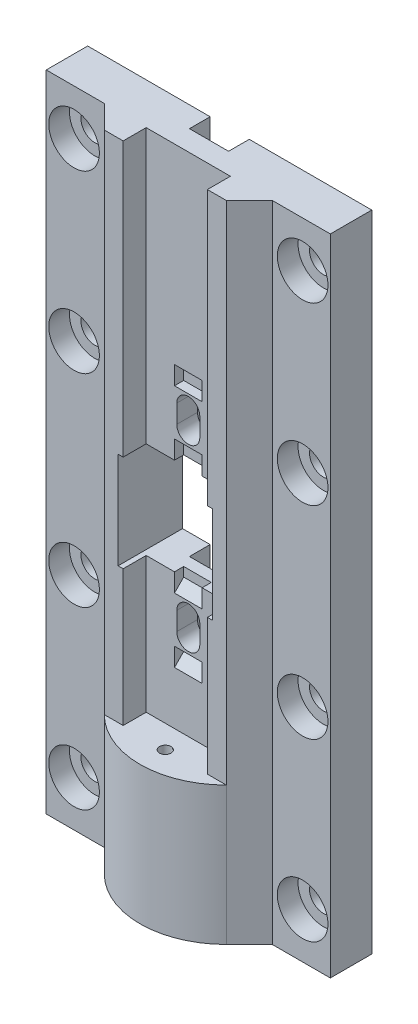
SolidWorks part; units mm, degrees
ref_plane "Top Plane" through (0, 0, 0) normal (0, 0, 1) x (1, 0, 0)
ref_plane "Right Plane" through (0, 0, 0) normal (0, 1, 0) x (1, 0, 0)
ref_plane "Front Plane" through (0, 0, 0) normal (1, 0, 0) x (0, 0, -1)
sketch "Sketch1" plane through (0, 0, 0) normal (0, 0, 1) x (1, 0, 0)
  line L0 (30.861, -28.956) -> (30.861, 28.956) construction
  line L1 (30.861, 28.956) -> (4.25, 28.956)
  line L2 (30.861, 28.956) -> (30.861, -41.044)
  line L3 (30.861, -41.044) -> (4.25, -41.044)
  line L4 (-30.861, 28.956) -> (-30.861, -41.044)
  line L5 (30.861, 28.956) -> (19.431, 28.956) construction
  line L6 (-30.861, -28.956) -> (-30.861, 28.956) construction
  line L8 (-24.8158, -19.05) -> (24.8412, -19.05) construction
  line L9 (-24.8158, -19.05) -> (-24.8158, 19.05) construction
  line L10 (-24.8158, 19.05) -> (24.8412, 19.05) construction
  line L11 (24.8412, -19.05) -> (24.8412, 19.05) construction
  line L12 (-4.25, 28.956) -> (-30.861, 28.956)
  line L14 (-4.25, -41.044) -> (-4.25, 28.956)
  line L16 (4.25, -41.044) -> (4.25, 28.956)
  line L17 (-4.25, -41.044) -> (-30.861, -41.044)
  circle A0 centre (24.8412, 19.05) radius 3
  circle A1 centre (24.8412, -19.05) radius 3
  circle A2 centre (-24.8158, -19.05) radius 3
  circle A3 centre (-24.8158, 19.05) radius 3
  arc A4 (-24.8158, 16.3957) -> (-24.8158, 21.7043) centre (-24.8158, 19.05) ccw construction
  arc A5 (24.8412, -21.7043) -> (24.8412, -16.3957) centre (24.8412, -19.05) ccw construction
  dimension "D1" = 6
  dimension "D2" = 70
  dimension "D3" = 8.5
extrude "Boss-Extrude1" add sketch "Sketch1" along normal blind 4.5
sketch "Sketch2" plane through (0, 0, 4.5) normal (0, 0, 1) x (1, 0, 0)
  line L1 (-30.861, 28.956) -> (30.861, 28.956)
  line L2 (-30.861, 28.956) -> (-30.861, -41.044)
  line L3 (-30.861, -41.044) -> (30.861, -41.044)
  line L4 (30.861, 28.956) -> (30.861, -41.044)
  circle A0 centre (24.8412, 19.05) radius 3 construction
  circle A1 centre (24.8412, -19.05) radius 3 construction
  circle A2 centre (-24.8158, 19.05) radius 3 construction
  circle A3 centre (-24.8158, -19.05) radius 3 construction
  circle A4 centre (24.8412, 19.05) radius 3 construction
  circle A5 centre (24.8412, -19.05) radius 3 construction
  circle A6 centre (-24.8158, 19.05) radius 3 construction
  circle A7 centre (-24.8158, -19.05) radius 3 construction
  circle A8 centre (24.8412, -19.05) radius 5.5
  circle A9 centre (-24.8158, -19.05) radius 5.5
  circle A10 centre (-24.8158, 19.05) radius 5.5
  circle A11 centre (24.8412, 19.05) radius 5.5
  dimension "D1" = 2.5
extrude "Boss-Extrude2" add sketch "Sketch2" along normal blind 4.5
sketch "Sketch3" plane through (0, 0, 9) normal (0, 0, 1) x (1, 0, 0)
  line L0 (-30.861, -41.044) -> (30.861, -41.044) construction
  line L1 (13.25, -41.044) -> (10.25, -41.044)
  line L2 (13.25, -41.044) -> (13.25, 28.956)
  line L3 (13.25, 28.956) -> (10.25, 28.956)
  line L4 (-13.25, -41.044) -> (-13.25, 28.956)
  line L5 (30.861, 28.956) -> (-30.861, 28.956) construction
  line L6 (-10.25, -41.044) -> (-13.25, -41.044)
  line L8 (10.25, -41.044) -> (10.25, 28.956)
  line L10 (-10.25, -41.044) -> (-10.25, 28.956)
  line L11 (-10.25, 28.956) -> (-13.25, 28.956)
  line L12 (30.861, -41.044) -> (13.25, -41.044) construction
  line L13 (-13.25, -41.044) -> (-30.861, -41.044) construction
  dimension "D1" = 20.5
  dimension "D2" = 3
extrude "Boss-Extrude3" add sketch "Sketch3" along normal blind 5
chamfer "Chamfer1" distance 5 angle 45 2 edges at (-13.25, -6.044, 9) (13.25, -6.044, 9)
sketch "Sketch4" plane through (0, 0, 9) normal (0, 0, 1) x (1, 0, 0)
  line L0 (-10.25, -41.044) -> (-10.25, 28.956) construction
  line L1 (10.25, -41.044) -> (-10.25, -41.044)
  line L2 (10.25, -41.044) -> (10.25, -30.544)
  line L3 (10.25, -30.544) -> (-10.25, -30.544)
  line L4 (-10.25, -41.044) -> (-10.25, -30.544)
  line L5 (0, -23.544) -> (0, -19.544) construction
  line L6 (-2.5, -23.544) -> (-2.5, -19.544)
  line L7 (2.5, -23.544) -> (2.5, -19.544)
  arc A0 (-2.5, -23.544) -> (2.5, -23.544) centre (0, -23.544) ccw
  arc A1 (2.5, -19.544) -> (-2.5, -19.544) centre (0, -19.544) ccw
  point P10 (0, -21.544)
  dimension "D2" = 2.5
  dimension "D1" = 10.5
  dimension "D3" = 7
  dimension "D4" = 4
extrude "Cut-Extrude1" cut sketch "Sketch4" against normal through all both and the other way through all
mirror "Mirror1" about plane through (30.861, -41.044, 4.5) normal (0, 1, 0) of bodies 106
ref_plane "Plane1" through (0, -41.044, 0) normal (0, -1, 0) x (-1, 0, 0)
sketch "Sketch5" plane through (0, -111.044, 0) normal (0, -1, 0) x (1, 0, 0)
  line L0 (-18.25, 9) -> (-13.25, 14) construction
  line L2 (-13.25, 14) -> (13.25, 14) construction
  line L3 (-13.25, 14) -> (-13.25, 9)
  line L4 (-13.25, 9) -> (13.25, 9)
  line L5 (13.25, 14) -> (13.25, 9)
  arc A0 (-13.25, 14) -> (13.25, 14) centre (0, 0.75) cw
  circle A1 centre (0, 14) radius 1.25
  dimension "D1" = 2.5
extrude "Boss-Extrude4" add sketch "Sketch5" against normal blind 30
sketch "Sketch6" plane through (0, 0, 9) normal (0, 0, 1) x (1, 0, 0)
  line L0 (10.25, 28.956) -> (-10.25, 28.956) construction
  line L1 (-10.25, -30.544) -> (-9.15, -30.544)
  line L2 (-10.25, -30.544) -> (-10.25, 28.956)
  line L3 (-10.25, 28.956) -> (-9.15, 28.956)
  line L4 (-9.15, -30.544) -> (-9.15, 28.956)
  line L6 (10.25, -30.544) -> (9.15, -30.544)
  line L7 (10.25, -30.544) -> (10.25, 28.956)
  line L8 (10.25, 28.956) -> (9.15, 28.956)
  line L9 (9.15, -30.544) -> (9.15, 28.956)
  dimension "D1" = 18.3
extrude "Boss-Extrude5" add sketch "Sketch6" along normal up to surface (5 mm away) up to face at (11.75, -26.044, 14)
sketch "Sketch7" plane through (0, 0, 9) normal (0, 0, 1) x (1, 0, 0)
  line L0 (0, -16.544) -> (0, -30.544) construction
  line L1 (3, -12.544) -> (-3, -12.544)
  line L2 (3, -12.544) -> (3, -16.544)
  line L3 (3, -16.544) -> (-3, -16.544)
  line L4 (-3, -12.544) -> (-3, -16.544)
  line L5 (9.15, -30.544) -> (-9.15, -30.544) construction
  line L7 (3, -30.544) -> (-3, -30.544)
  line L8 (3, -30.544) -> (3, -26.544)
  line L9 (3, -26.544) -> (-3, -26.544)
  line L10 (-3, -30.544) -> (-3, -26.544)
  dimension "D1" = 6
  dimension "D2" = 18
  dimension "D3" = 14
  dimension "D4" = 4
extrude "Cut-Extrude2" cut sketch "Sketch7" against normal blind 2
chamfer "Chamfer2" distance 2 angle 45 1 edges at (0, -26.544, 7)
chamfer "Chamfer3" distance 2 angle 45 1 edges at (0, -12.544, 7)
mirror "Mirror2" about plane through (0, -41.044, 0) normal (0, -1, 0) of "Chamfer3", "Chamfer2", "Cut-Extrude2", "Boss-Extrude5"
